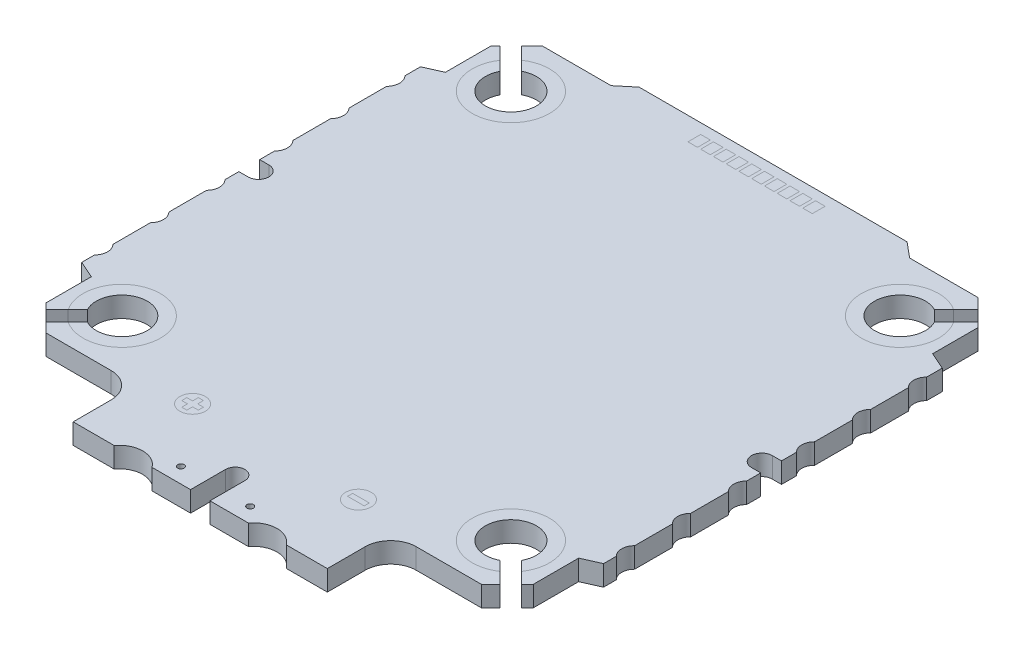
SolidWorks part; units mm, degrees
ref_plane "Front Plane" through (0, 0, 0) normal (0, 0, 1) x (1, 0, 0)
ref_plane "Top Plane" through (0, 0, 0) normal (0, 1, 0) x (1, 0, 0)
ref_plane "Right Plane" through (0, 0, 0) normal (1, 0, 0) x (0, 0, -1)
sketch "Эскиз1" plane through (0, 0, 0) normal (0, 1, 0) x (1, 0, 0)
  line L0 (-23.1026, -8.1757) -> (224.8974, -8.1757) construction
  line L1 (22.55, 116.05) -> (194.55, 116.05) construction
sketch "Эскиз2" plane through (0, 0, 0) normal (0, 1, 0) x (1, 0, 0)
  line L0 (0, 22.45) -> (0, -22.45) construction
  line L1 (-10.5, 22.45) -> (10.5, 22.45)
  line L2 (10.5, 22.45) -> (11.7, 21.45)
  line L3 (11.7, 21.45) -> (17.06, 21.45)
  line L4 (-20.45, 0) -> (20.45, 0) construction
  line L5 (17.06, 21.45) -> (19.1, 19.41)
  line L6 (19.1, 19.41) -> (19.1, 15.86)
  line L7 (19.1, 15.86) -> (20.45, 15.26)
  line L8 (20.45, 15.26) -> (20.45, -11.29)
  line L9 (20.45, -11.29) -> (19.1, -11.89)
  line L10 (19.1, -11.89) -> (19.1, -15.44)
  line L11 (19.1, -15.44) -> (17.06, -17.48)
  line L12 (-2.4749, 2.4749) -> (2.4749, -2.4749) construction
  line L13 (-2.4749, -2.4749) -> (2.4749, 2.4749) construction
  line L14 (17.06, -17.48) -> (9.96, -17.48)
  line L15 (9.96, -17.48) -> (9.96, -22.45)
  line L16 (9.96, -22.45) -> (0.76, -22.45)
  line L17 (0.76, -22.45) -> (0.76, -18.95)
  line L18 (0.76, -18.95) -> (-0.76, -18.95)
  line L19 (-10.5, 22.45) -> (-11.7, 21.45)
  line L20 (-11.7, 21.45) -> (-17.06, 21.45)
  line L21 (-17.06, 21.45) -> (-19.1, 19.41)
  line L22 (-19.1, 19.41) -> (-19.1, 15.86)
  line L23 (-19.1, 15.86) -> (-20.45, 15.26)
  line L24 (-20.45, 15.26) -> (-20.45, -11.29)
  line L25 (-20.45, -11.29) -> (-19.1, -11.89)
  line L26 (-19.1, -11.89) -> (-19.1, -15.44)
  line L27 (-19.1, -15.44) -> (-17.06, -17.48)
  line L28 (-17.06, -17.48) -> (-9.96, -17.48)
  line L29 (-9.96, -17.48) -> (-9.96, -22.45)
  line L30 (-9.96, -22.45) -> (-0.76, -22.45)
  line L31 (-0.76, -22.45) -> (-0.76, -18.95)
  line L33 (-15.25, -13.35) -> (15.25, -13.35) construction
  line L34 (-15.25, -13.35) -> (-15.25, 17.15) construction
  line L35 (-15.25, 17.15) -> (15.25, 17.15) construction
  line L36 (15.25, -13.35) -> (15.25, 17.15) construction
  line L37 (-15.25, -13.35) -> (15.25, 17.15) construction
  line L38 (-15.25, 17.15) -> (15.25, -13.35) construction
  circle A0 centre (15.25, 17.15) radius 2
  circle A1 centre (15.25, -13.35) radius 2
  circle A2 centre (-15.25, -13.35) radius 2
  circle A3 centre (-15.25, 17.15) radius 2
  point P5 (0, 0)
  point P10 (0, 0)
  point P15 (0, 0)
  point P18 (0, 0)
  point P28 (0, 1.9)
  point P50 (0, -18.95)
  dimension "D20" = 4
  dimension "D1" = 44.9
  dimension "D2" = 40.9
  dimension "D3" = 45
  dimension "D4" = 7
  dimension "D5" = 45
  dimension "D6" = 7
  dimension "D7" = 1.2
  dimension "D8" = 1
  dimension "D9" = 5.36
  dimension "D10" = 10.5
  dimension "D11" = 19.1
  dimension "D12" = 3.55
  dimension "D13" = 0.6
  dimension "D14" = 0.6
  dimension "D15" = 26.55
  dimension "D16" = 7.1
  dimension "D17" = 9.2
  dimension "D18" = 3.5
  dimension "D19" = 30.5
  dimension "D21" = 1.9
extrude "Бобышка-Вытянуть1" add sketch "Эскиз2" along normal blind 1.6
sketch "Эскиз4" plane through (0, 0, 0) normal (0, 1, 0) x (1, 0, 0)
  line L0 (-17.0233, 18.0748) -> (-18.7293, 19.7807)
  line L1 (-17.06, 21.45) -> (-19.1, 19.41) construction
  line L2 (-18.7293, 19.7807) -> (-17.8807, 20.6293)
  line L3 (-17.8807, 20.6293) -> (-16.1748, 18.9233)
  line L4 (-15.25, 17.15) -> (-15.25, 19.15) construction
  line L5 (-15.25, 17.15) -> (-16.6642, 18.5642) construction
  line L6 (-15.25, 17.15) -> (15.25, 17.15) construction
  line L7 (15.25, 17.15) -> (15.25, -13.35) construction
  line L8 (15.25, -13.35) -> (-15.25, -13.35) construction
  line L9 (-15.25, -13.35) -> (-15.25, 17.15) construction
  line L10 (-15.25, 1.9) -> (15.25, 1.9) construction
  line L11 (0, 17.15) -> (0, -13.35) construction
  line L12 (17.8807, 20.6293) -> (16.1748, 18.9233)
  line L13 (18.7293, 19.7807) -> (17.8807, 20.6293)
  line L14 (17.0233, 18.0748) -> (18.7293, 19.7807)
  line L15 (-15.25, -13.35) -> (-16.6642, -14.7642) construction
  line L16 (-17.7957, -16.7443) -> (-18.6443, -15.8957)
  line L17 (-19.1, -15.44) -> (-17.06, -17.48) construction
  line L18 (-18.6443, -15.8957) -> (-17.0233, -14.2748)
  line L19 (-17.7957, -16.7443) -> (-16.1748, -15.1233)
  line L20 (18.6443, -15.8957) -> (17.0233, -14.2748)
  line L21 (17.7957, -16.7443) -> (18.6443, -15.8957)
  line L22 (17.7957, -16.7443) -> (16.1748, -15.1233)
  circle A0 centre (-15.25, 17.15) radius 2 construction
  arc A1 (-17.0233, 18.0748) -> (-16.1748, 18.9233) centre (-15.25, 17.15) ccw
  circle A2 centre (15.25, 17.15) radius 2 construction
  arc A3 (16.1748, 18.9233) -> (17.0233, 18.0748) centre (15.25, 17.15) ccw
  circle A4 centre (-15.25, -13.35) radius 2 construction
  arc A5 (-16.1748, -15.1233) -> (-17.0233, -14.2748) centre (-15.25, -13.35) ccw
  circle A6 centre (15.25, -13.35) radius 2 construction
  arc A7 (17.0233, -14.2748) -> (16.1748, -15.1233) centre (15.25, -13.35) ccw
  dimension "D1" = 1.2
  dimension "D2" = 45
  dimension "D3" = 1.2
extrude "Вырез-Вытянуть1" cut sketch "Эскиз4" along normal through all
sketch "Эскиз5" plane through (0, 0, 0) normal (0, 1, 0) x (1, 0, 0)
  line L0 (-17.0233, 18.0748) -> (-17.7744, 18.8258)
  line L1 (-18.7293, 19.7807) -> (-17.0233, 18.0748) construction
  line L2 (-16.1748, 18.9233) -> (-16.9258, 19.6744)
  line L3 (-16.1748, 18.9233) -> (-17.8807, 20.6293) construction
  line L4 (16.1748, 18.9233) -> (16.9258, 19.6744)
  line L5 (17.8807, 20.6293) -> (16.1748, 18.9233) construction
  line L6 (17.0233, 18.0748) -> (17.7744, 18.8258)
  line L7 (17.0233, 18.0748) -> (18.7293, 19.7807) construction
  line L8 (16.1748, -15.1233) -> (16.9258, -15.8744)
  line L9 (16.1748, -15.1233) -> (17.7957, -16.7443) construction
  line L10 (17.0233, -14.2748) -> (17.7744, -15.0258)
  line L11 (18.6443, -15.8957) -> (17.0233, -14.2748) construction
  line L12 (-16.1748, -15.1233) -> (-16.9258, -15.8744)
  line L13 (-17.7957, -16.7443) -> (-16.1748, -15.1233) construction
  line L14 (-17.0233, -14.2748) -> (-17.7744, -15.0258)
  line L15 (-17.0233, -14.2748) -> (-18.6443, -15.8957) construction
  arc A0 (-16.1748, -15.1233) -> (-17.0233, -14.2748) centre (-15.25, -13.35) ccw construction
  arc A1 (-16.1748, -15.1233) -> (-17.0233, -14.2748) centre (-15.25, -13.35) ccw
  arc A2 (17.0233, -14.2748) -> (16.1748, -15.1233) centre (15.25, -13.35) ccw construction
  arc A3 (17.0233, -14.2748) -> (16.1748, -15.1233) centre (15.25, -13.35) ccw
  arc A4 (16.1748, 18.9233) -> (17.0233, 18.0748) centre (15.25, 17.15) ccw construction
  arc A5 (16.1748, 18.9233) -> (17.0233, 18.0748) centre (15.25, 17.15) ccw
  arc A6 (-17.0233, 18.0748) -> (-16.1748, 18.9233) centre (-15.25, 17.15) ccw construction
  arc A7 (-17.0233, 18.0748) -> (-16.1748, 18.9233) centre (-15.25, 17.15) ccw
  arc A8 (-17.7744, 18.8258) -> (-16.9258, 19.6744) centre (-15.25, 17.15) ccw
  arc A9 (16.9258, 19.6744) -> (17.7744, 18.8258) centre (15.25, 17.15) ccw
  arc A10 (17.7744, -15.0258) -> (16.9258, -15.8744) centre (15.25, -13.35) ccw
  arc A11 (-16.9258, -15.8744) -> (-17.7744, -15.0258) centre (-15.25, -13.35) ccw
  dimension "D1" = 1.03
extrude "Вырез-Вытянуть2" cut sketch "Эскиз5" along normal through all
extrude "Бобышка-Вытянуть2" add sketch "Эскиз5<2>" along normal up to surface (1.6 mm away) separate body up to face at (0, 1.6, 0.2809)
sketch "Эскиз5<2>" plane through (0, 0, 0) normal (0, 1, 0) x (1, 0, 0) same geometry as "Эскиз5"
fillet "Скругление1" 2 edges at (-0.76, 0.8, 18.95) (0.76, 0.8, 18.95) type full round first side face at (-0.76, 0.8, 20.7) second side face at (0.76, 0.8, 20.7) middle face at (0, 0.8, 18.95)
fillet "Скругление2" radius 2 2 edges at (-9.96, 0.8, 17.48) (9.96, 0.8, 17.48)
sketch "Эскиз6" plane through (0, 0, 0) normal (0, 1, 0) x (1, 0, 0)
  line L0 (3.78, -22.45) -> (6.75, -22.45)
  line L1 (0.76, -22.45) -> (9.96, -22.45) construction
  line L2 (20.45, 2.66) -> (20.45, 1.03)
  line L3 (20.45, -11.29) -> (20.45, 15.26) construction
  line L4 (20.45, 2.66) -> (19.728, 2.66)
  line L5 (20.45, 1.03) -> (19.728, 1.03)
  line L6 (20.45, -8.8495) -> (20.45, -10.2865)
  line L7 (20.45, 3.8264) -> (20.45, 5.2604)
  line L8 (20.45, -4.4595) -> (20.45, -5.8965)
  line L9 (20.45, -0.0695) -> (20.45, -1.5065)
  line L10 (20.45, 8.2164) -> (20.45, 9.6504)
  line L11 (20.45, 12.6064) -> (20.45, 14.0404)
  arc A0 (6.75, -22.45) -> (3.78, -22.45) centre (5.265, -23.5365) ccw
  arc A1 (19.728, 2.66) -> (19.728, 1.03) centre (19.728, 1.845) ccw
  arc A2 (20.45, -10.2865) -> (20.45, -8.8495) centre (21.1685, -9.568) cw
  arc A3 (20.45, 3.8264) -> (20.45, 5.2604) centre (21.17, 4.5434) cw
  arc A4 (20.45, -5.8965) -> (20.45, -4.4595) centre (21.1685, -5.178) cw
  arc A5 (20.45, -1.5065) -> (20.45, -0.0695) centre (21.1685, -0.788) cw
  arc A6 (20.45, 8.2164) -> (20.45, 9.6504) centre (21.17, 8.9334) cw
  arc A7 (20.45, 12.6064) -> (20.45, 14.0404) centre (21.17, 13.3234) cw
  dimension "D2" = 1.84
  dimension "D6" = 0.815
  dimension "D11" = 1.0161
  dimension "D15" = 0.72
  dimension "D1" = 2.97
  dimension "D3" = 3.78
  dimension "D4" = 1.03
  dimension "D5" = 1.63
  dimension "D7" = 0.722
  dimension "D8" = 0.722
  dimension "D12" = 0.7185
  dimension "D13" = 12.1635
  dimension "D14" = 14.1129
  dimension "D9" = 3
  dimension "D10" = 3
extrude "Вырез-Вытянуть3" cut sketch "Эскиз6" along normal through all
mirror "Зеркальное отражение1" about plane through (0, 0, 0) normal (1, 0, 0) of "Вырез-Вытянуть3"
ref_plane "Плоскость1" through (0, 0, -1.845) normal (0, 0, 1) x (1, 0, 0)
sketch "Эскиз7" plane through (0, 1.6, 0) normal (0, 1, 0) x (1, 0, 0)
  circle A1 centre (-2.715, -21.25) radius 0.25
  circle A2 centre (2.715, -21.25) radius 0.25
  dimension "D1" = 0.5
  dimension "D2" = 0.5
extrude "Вырез-Вытянуть4" cut sketch "Эскиз7" against normal through all
sketch "Эскиз8" plane through (0, 0, 0) normal (0, 1, 0) x (1, 0, 0)
  line L0 (10.5, 22.45) -> (-10.5, 22.45) construction
  line L1 (-4.875, 20.65) -> (-4.125, 20.65)
  line L2 (-4.875, 20.65) -> (-4.875, 21.65)
  line L3 (-4.875, 21.65) -> (-4.125, 21.65)
  line L4 (-4.125, 20.65) -> (-4.125, 21.65)
  line L5 (-4.875, 20.65) -> (-4.125, 21.65) construction
  line L6 (-4.875, 21.65) -> (-4.125, 20.65) construction
  line L7 (-3.875, 20.65) -> (-3.125, 20.65)
  line L8 (-3.875, 20.65) -> (-3.875, 21.65)
  line L9 (-3.875, 21.65) -> (-3.125, 21.65)
  line L10 (-3.125, 20.65) -> (-3.125, 21.65)
  line L11 (-3.875, 20.65) -> (-3.125, 21.65) construction
  line L12 (-3.875, 21.65) -> (-3.125, 20.65) construction
  line L13 (-2.875, 20.65) -> (-2.125, 20.65)
  line L14 (-2.875, 20.65) -> (-2.875, 21.65)
  line L15 (-2.875, 21.65) -> (-2.125, 21.65)
  line L16 (-2.125, 20.65) -> (-2.125, 21.65)
  line L17 (-2.875, 20.65) -> (-2.125, 21.65) construction
  line L18 (-2.875, 21.65) -> (-2.125, 20.65) construction
  line L19 (-1.875, 20.65) -> (-1.125, 20.65)
  line L20 (-1.875, 20.65) -> (-1.875, 21.65)
  line L21 (-1.875, 21.65) -> (-1.125, 21.65)
  line L22 (-1.125, 20.65) -> (-1.125, 21.65)
  line L23 (-1.875, 20.65) -> (-1.125, 21.65) construction
  line L24 (-1.875, 21.65) -> (-1.125, 20.65) construction
  line L25 (-0.875, 20.65) -> (-0.125, 20.65)
  line L26 (-0.875, 20.65) -> (-0.875, 21.65)
  line L27 (-0.875, 21.65) -> (-0.125, 21.65)
  line L28 (-0.125, 20.65) -> (-0.125, 21.65)
  line L29 (-0.875, 20.65) -> (-0.125, 21.65) construction
  line L30 (-0.875, 21.65) -> (-0.125, 20.65) construction
  line L31 (0.125, 20.65) -> (0.875, 20.65)
  line L32 (0.125, 20.65) -> (0.125, 21.65)
  line L33 (0.125, 21.65) -> (0.875, 21.65)
  line L34 (0.875, 20.65) -> (0.875, 21.65)
  line L35 (0.125, 20.65) -> (0.875, 21.65) construction
  line L36 (0.125, 21.65) -> (0.875, 20.65) construction
  line L37 (1.125, 20.65) -> (1.875, 20.65)
  line L38 (1.125, 20.65) -> (1.125, 21.65)
  line L39 (1.125, 21.65) -> (1.875, 21.65)
  line L40 (1.875, 20.65) -> (1.875, 21.65)
  line L41 (1.125, 20.65) -> (1.875, 21.65) construction
  line L42 (1.125, 21.65) -> (1.875, 20.65) construction
  line L43 (2.125, 20.65) -> (2.875, 20.65)
  line L44 (2.125, 20.65) -> (2.125, 21.65)
  line L45 (2.125, 21.65) -> (2.875, 21.65)
  line L46 (2.875, 20.65) -> (2.875, 21.65)
  line L47 (2.125, 20.65) -> (2.875, 21.65) construction
  line L48 (2.125, 21.65) -> (2.875, 20.65) construction
  line L49 (3.125, 20.65) -> (3.875, 20.65)
  line L50 (3.125, 20.65) -> (3.125, 21.65)
  line L51 (3.125, 21.65) -> (3.875, 21.65)
  line L52 (3.875, 20.65) -> (3.875, 21.65)
  line L53 (3.125, 20.65) -> (3.875, 21.65) construction
  line L54 (3.125, 21.65) -> (3.875, 20.65) construction
  line L55 (4.125, 20.65) -> (4.875, 20.65)
  line L56 (4.125, 20.65) -> (4.125, 21.65)
  line L57 (4.125, 21.65) -> (4.875, 21.65)
  line L58 (4.875, 20.65) -> (4.875, 21.65)
  line L59 (4.125, 20.65) -> (4.875, 21.65) construction
  line L60 (4.125, 21.65) -> (4.875, 20.65) construction
  point P0 (-4.5, 21.15)
  point P5 (-3.5, 21.15)
  point P11 (-2.5, 21.15)
  point P16 (-1.5, 21.15)
  point P21 (-0.5, 21.15)
  point P26 (0.5, 21.15)
  point P31 (1.5, 21.15)
  point P36 (2.5, 21.15)
  point P41 (3.5, 21.15)
  point P46 (4.5, 21.15)
  dimension "D1" = 5.625
  dimension "D2" = 1
  dimension "D3" = 1
  dimension "D4" = 1
  dimension "D5" = 1
  dimension "D6" = 1
  dimension "D7" = 1
  dimension "D8" = 1
  dimension "D9" = 1
  dimension "D10" = 1
  dimension "D11" = 0.75
  dimension "D12" = 1
  dimension "D13" = 0.8
  dimension "D14" = 5.625
wrap "Перенос1" sketch "Эскиз8" wrap type scribe source sketch "Эскиз8" face at (-2.715, 1.6, 21.5)
sketch "Эскиз9" plane through (0, 0, 0) normal (0, 1, 0) x (1, 0, 0)
  line L0 (0, -18.95) -> (0, -14.77) construction
  line L1 (-4.3605, -14.77) -> (4.3605, -14.77) construction
  line L2 (-6.5, -16.55) -> (6.5, -16.55) construction
  line L3 (-3.78, -22.45) -> (-0.76, -22.45) construction
  line L4 (-6.7, -16.35) -> (-6.7, -15.9)
  line L5 (-7.15, -16.75) -> (-6.7, -16.75)
  line L6 (-7.15, -16.75) -> (-7.15, -16.35)
  line L7 (-7.15, -16.35) -> (-6.7, -16.35)
  line L8 (-5.85, -16.75) -> (-5.85, -16.35)
  line L9 (-7.15, -16.75) -> (-5.85, -16.35) construction
  line L10 (-7.15, -16.35) -> (-5.85, -16.75) construction
  line L11 (-6.7, -17.2) -> (-6.3, -17.2)
  line L12 (-6.7, -17.2) -> (-6.7, -16.75)
  line L13 (-6.7, -15.9) -> (-6.3, -15.9)
  line L14 (-6.3, -17.2) -> (-6.3, -16.75)
  line L15 (-6.7, -17.2) -> (-6.3, -15.9) construction
  line L16 (-6.7, -15.9) -> (-6.3, -17.2) construction
  line L17 (5.85, -16.75) -> (7.15, -16.75)
  line L18 (5.85, -16.75) -> (5.85, -16.35)
  line L19 (5.85, -16.35) -> (7.15, -16.35)
  line L20 (7.15, -16.75) -> (7.15, -16.35)
  line L21 (5.85, -16.75) -> (7.15, -16.35) construction
  line L22 (5.85, -16.35) -> (7.15, -16.75) construction
  line L23 (-6.3, -16.75) -> (-5.85, -16.75)
  line L24 (-6.3, -16.35) -> (-6.3, -15.9)
  line L25 (-6.3, -16.35) -> (-5.85, -16.35)
  line L26 (-6.7, -15.9) -> (-6.7, -17.2) construction
  line L27 (-6.3, -15.9) -> (-6.3, -17.2) construction
  arc A0 (0.76, -19.71) -> (-0.76, -19.71) centre (0, -19.71) ccw construction
  circle A1 centre (-6.5, -16.55) radius 1
  circle A2 centre (6.5, -16.55) radius 1
  point P11 (0, -16.55)
  dimension "D1" = 2
  dimension "D2" = 5.9
  dimension "D3" = 13
  dimension "D4" = 1.3
  dimension "D5" = 0.4
  dimension "D6" = 1.3
wrap "Перенос2" sketch "Эскиз9" wrap type scribe source sketch "Эскиз9" face at (4.5, 1.6, -21.15)
